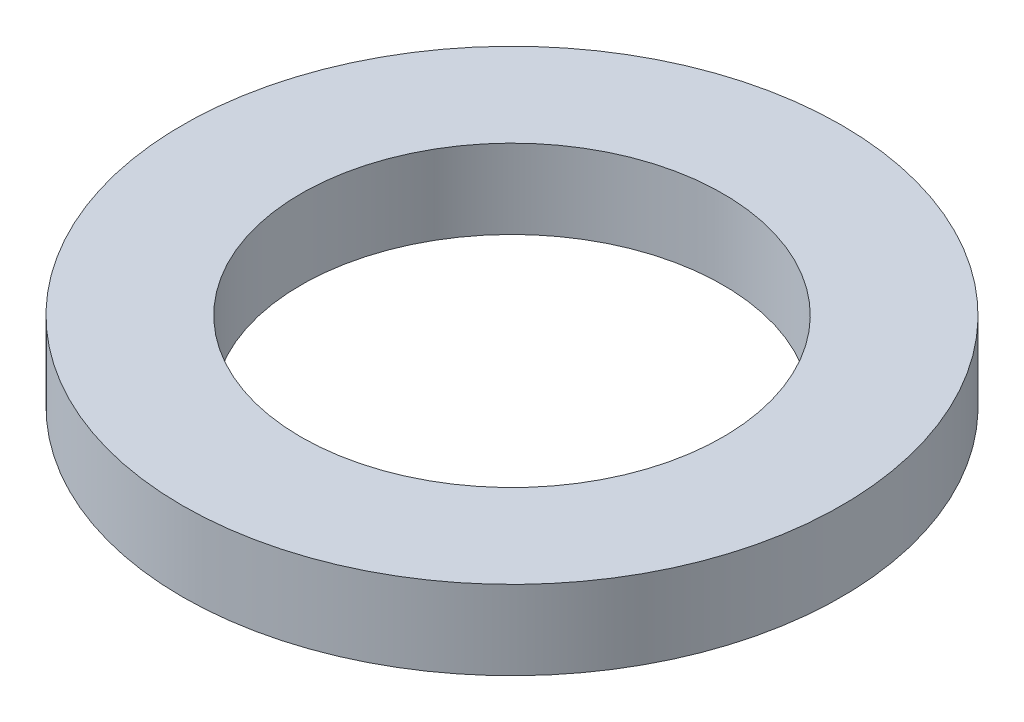
SolidWorks part; units mm, degrees
ref_plane "Front Plane" through (0, 0, 0) normal (0, 0, 1) x (1, 0, 0)
ref_plane "Top Plane" through (0, 0, 0) normal (0, 1, 0) x (1, 0, 0)
ref_plane "Right Plane" through (0, 0, 0) normal (1, 0, 0) x (0, 0, -1)
sketch "Sketch1" plane through (0, 0, 0) normal (0, 1, 0) x (1, 0, 0)
  circle A0 centre (0, 0) radius 62.5
  dimension "FLANGE_OD" = 125
extrude "Boss-Extrude1" add sketch "Sketch1" along normal blind 15
sketch "Sketch2" plane through (0, 0, 0) normal (0, 1, 0) x (1, 0, 0)
  circle A0 centre (0, 0) radius 40
  dimension "BORE_D" = 80
extrude "Cut-Extrude1" cut sketch "Sketch2" along normal through all
sketch "Sketch3" plane through (0, 15, 0) normal (0, 1, 0) x (1, 0, 0)
  circle A0 centre (0, 0) radius 27.5926 construction
  circle A1 centre (-27.5926, 0) radius 3.5103
  dimension "BOLT_D" = 7.0206
  dimension "BOLT_PCD" = 55.1851
extrude "Cut-Extrude2" cut sketch "Sketch3" against normal blind 14.4724 rebuild error yes
pattern_circular "CirPattern1" count 5 over 360 rebuild error yes
